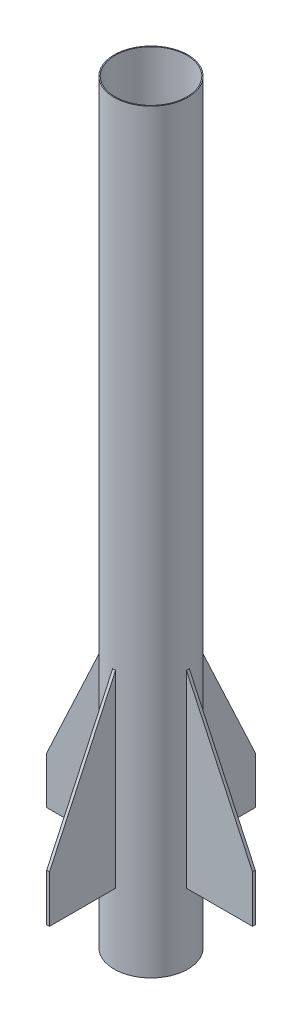
SolidWorks part; units mm, degrees
ref_plane "Front Plane" through (0, 0, 0) normal (0, 0, 1) x (1, 0, 0)
ref_plane "Top Plane" through (0, 0, 0) normal (0, 1, 0) x (1, 0, 0)
ref_plane "Right Plane" through (0, 0, 0) normal (1, 0, 0) x (0, 0, -1)
sketch "Sketch1" plane through (0, 0, 0) normal (0, 0, 1) x (1, 0, 0)
  line L0 (78.16, 0) -> (78.16, 1600)
  line L1 (0, 0) -> (0, 2000) construction
  line L9 (76.2, 0) -> (76.2, 1600)
  line L10 (78.16, 0) -> (76.2, 0)
  line L11 (78.16, 1600) -> (76.2, 1600)
  point P7 (65, 1600)
  point P8 (-1029.1667, 1600)
  point P9 (-9.3208, 1996.3774)
  dimension "D1" = 1600
  dimension "D2" = 76.2
  dimension "D3" = 2000
  dimension "D4" = 1.96
revolve "Revolve1" add sketch "Sketch1" angle 360 about L1
sketch "Sketch2" plane through (0, 0, 0) normal (0, 0, 1) x (1, 0, 0)
  line L5 (-78.16, 550) -> (-78.16, 150)
  line L6 (-78.16, 1600) -> (-78.16, 0) construction
  line L7 (-78.16, 150) -> (-218.16, 150)
  line L8 (-218.16, 150) -> (-218.16, 250)
  line L9 (-218.16, 250) -> (-78.16, 550)
  dimension "D1" = 400
  dimension "D2" = 140
  dimension "D3" = 100
  dimension "D4" = 150
extrude "Boss-Extrude1" add sketch "Sketch2" along normal blind 3 and the other way blind 3 separate body contours L9 L5 L7 L8
sketch "Sketch4" plane through (-78.16, 0, 0) normal (1, 0, 0) x (0, 0, -1)
  line L0 (3, 150) -> (-3, 150) construction
  line L1 (3, 550) -> (3, 150) construction
  line L2 (3, 550) -> (-3, 550) construction
  line L3 (-3, 550) -> (-3, 150) construction
  line L4 (3, 150) -> (-3, 150)
  line L5 (3, 550) -> (3, 150)
  line L6 (3, 550) -> (-3, 550)
  line L7 (-3, 550) -> (-3, 150)
sketch "Sketch5" plane through (0, 0, 0) normal (0, 0, 1) x (1, 0, 0)
  line L0 (0, 0) -> (0, 930.568) construction
pattern_circular "CirPattern2" count 4 over 360 about axis through (0, 0, 0) along (0, 1, 0) of bodies 102
